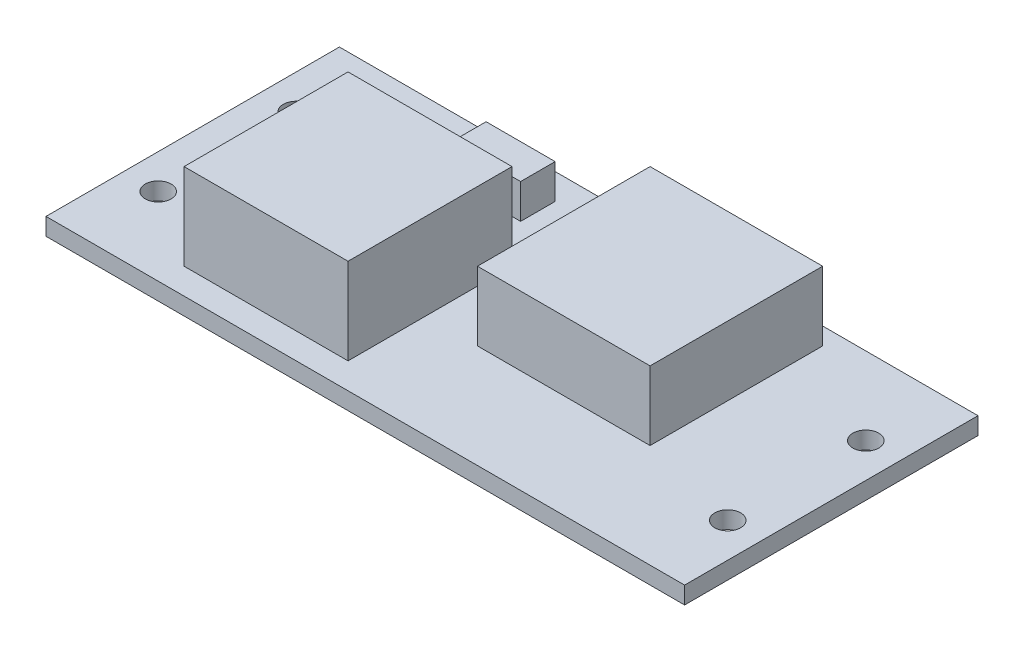
SolidWorks part; units mm, degrees
ref_plane "Front" through (0, 0, 0) normal (0, 0, 1) x (1, 0, 0)
ref_plane "Top" through (0, 0, 0) normal (0, 1, 0) x (1, 0, 0)
ref_plane "Right" through (0, 0, 0) normal (1, 0, 0) x (0, 0, -1)
sketch "Эскиз1" plane through (0, 0, 0) normal (0, 1, 0) x (1, 0, 0)
  line L0 (-18.5, 0) -> (18.5, 0) construction
  line L1 (-18.5, 8.5) -> (18.5, 8.5)
  line L2 (-18.5, 8.5) -> (-18.5, -8.5)
  line L3 (-18.5, -8.5) -> (18.5, -8.5)
  line L4 (18.5, 8.5) -> (18.5, -8.5)
  line L5 (-18.5, 8.5) -> (18.5, -8.5) construction
  line L6 (-18.5, -8.5) -> (18.5, 8.5) construction
  line L7 (0, 8.5) -> (0, -8.5) construction
  line L9 (-12, 2.5) -> (-2.5, 2.5)
  line L10 (-12, 2.5) -> (-12, -7)
  line L11 (-12, -7) -> (-2.5, -7)
  line L12 (-2.5, 2.5) -> (-2.5, -7)
  line L13 (0.5, 7.5) -> (10.5, 7.5)
  line L14 (0.5, 7.5) -> (0.5, -2.5)
  line L15 (0.5, -2.5) -> (10.5, -2.5)
  line L16 (10.5, 7.5) -> (10.5, -2.5)
  line L17 (-8.5, 7) -> (-4.5, 7)
  line L18 (-8.5, 7) -> (-8.5, 5)
  line L19 (-8.5, 5) -> (-4.5, 5)
  line L20 (-4.5, 7) -> (-4.5, 5)
  circle A0 centre (-16.5, 4) radius 0.75
  circle A1 centre (-16.5, -4) radius 0.75
  circle A2 centre (16.5, -4) radius 0.75
  circle A3 centre (16.5, 4) radius 0.75
  point P0 (0, 0)
  dimension "D13" = 1.5
  dimension "D14" = 2
  dimension "D15" = 4.5
  dimension "D1" = 37
  dimension "D2" = 17
  dimension "D3" = 9.5
  dimension "D4" = 1.5
  dimension "D5" = 6.5
  dimension "D6" = 1.5
  dimension "D7" = 4
  dimension "D8" = 2
  dimension "D9" = 10
  dimension "D10" = 10
  dimension "D11" = 8
  dimension "D12" = 1
extrude "Бобышка-Вытянуть1" add sketch "Эскиз1" against normal blind 1 contours L4 L1 L2 L3 L9 L12 L11 L10 L13 L16 L15 L14 L17 L20 L19 L18 | L12 L9 L10 L11 | L16 L13 L14 L15 | L20 L17 L18 L19 region at (0.3689, 0, 0.2241) region at (-7.25, 0, 2.25) region at (5.5, 0, -2.5) region at (-6.5, 0, -6)
extrude "Бобышка-Вытянуть2" add sketch "Эскиз1<3>" along normal blind 4 contours L16 L13 L14 L15 region at (5.5, 0, -2.5)
sketch "Эскиз1<3>" plane through (0, 0, 0) normal (0, 1, 0) x (1, 0, 0) same geometry as "Эскиз1"
extrude "Бобышка-Вытянуть3" add sketch "Эскиз1<4>" along normal blind 5 contours L12 L9 L10 L11 region at (-7.25, 0, 2.25)
sketch "Эскиз1<4>" plane through (0, 0, 0) normal (0, 1, 0) x (1, 0, 0) same geometry as "Эскиз1"
extrude "Бобышка-Вытянуть4" add sketch "Эскиз1<5>" along normal blind 2 contours L20 L17 L18 L19 region at (-6.5, 0, -6)
sketch "Эскиз1<5>" plane through (0, 0, 0) normal (0, 1, 0) x (1, 0, 0) same geometry as "Эскиз1"
